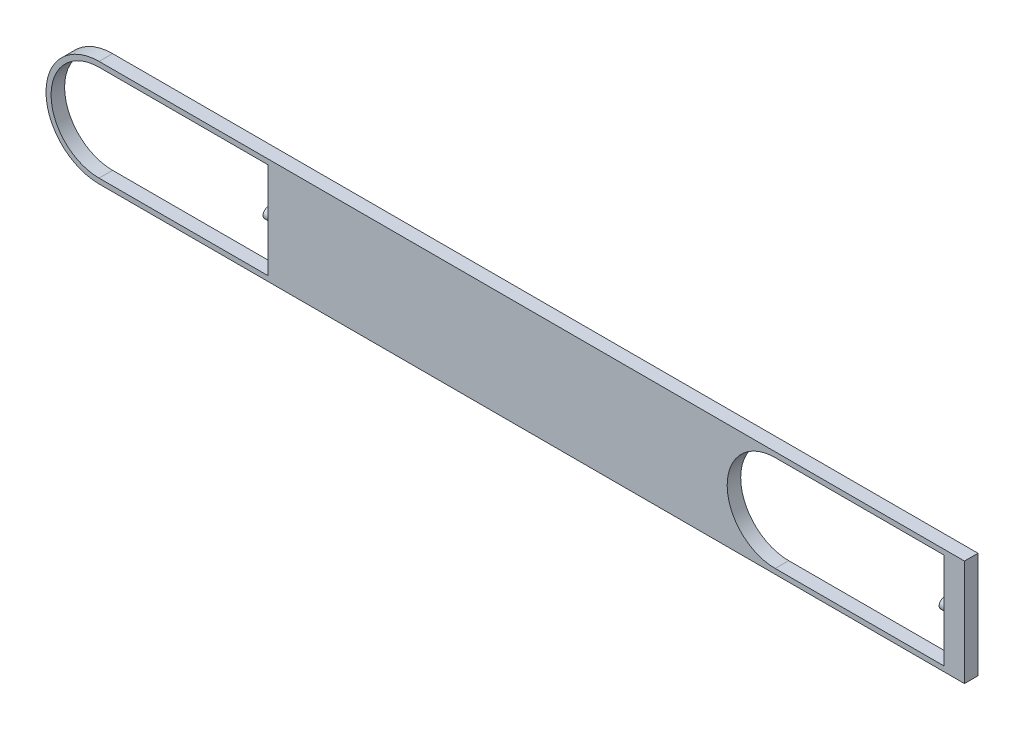
SolidWorks part; units mm, degrees
other "first"
other "second"
ref_plane "Front Plane" through (0, 0, 0) normal (0, 0, 1) x (1, 0, 0)
ref_plane "Top Plane" through (0, 0, 0) normal (0, 1, 0) x (1, 0, 0)
ref_plane "Right Plane" through (0, 0, 0) normal (1, 0, 0) x (0, 0, -1)
sketch "Sketch1" plane through (0, 0, 0) normal (0, 0, 1) x (1, 0, 0)
  circle A0 centre (0, 0) radius 19.939
  dimension "D1" = 39.878
extrude "circle extrude" add sketch "Sketch1" along normal blind 5.08
sketch "Sketch3" plane through (0, 0, 0) normal (1, 0, 0) x (0, 0, -1)
  line L0 (0, 55) -> (0, -55) construction
  line L1 (-5.08, 19.939) -> (0, 19.939)
  line L2 (-5.08, 19.939) -> (-5.08, -19.939)
  line L3 (-5.08, -19.939) -> (0, -19.939)
  line L4 (0, 19.939) -> (0, -19.939)
  line L5 (-5.08, -19.939) -> (0, -19.939) construction
extrude "rectangle extrude" add sketch "Sketch3" along normal blind 127
sketch "Sketch2" plane through (0, 0, 5.08) normal (0, 0, 1) x (1, 0, 0)
  circle A0 centre (0, 0) radius 18.034
  dimension "D1" = 36.068
extrude "circle cut" cut sketch "Sketch2" against normal through all
sketch "Sketch6" plane through (0, 0, 5.08) normal (0, 0, 1) x (1, 0, 0)
  line L1 (125.095, -18.034) -> (125.095, 18.034)
  line L3 (0, -18.034) -> (0, 18.034)
  line L4 (0, -18.034) -> (125.095, -18.034)
  line L5 (127, -19.939) -> (0, -19.939) construction
  line L6 (0, 18.034) -> (125.095, 18.034)
  line L8 (127, 19.939) -> (127, -19.939) construction
  arc A0 (0, 19.939) -> (0, -19.939) centre (0, 0) ccw construction
  circle A1 centre (0, 0) radius 18.034 construction
  point P5 (125.095, 0)
  point P12 (0, 0)
  point P17 (-19.939, 0)
  dimension "D1" = 1.905
  dimension "D2" = 1.905
  dimension "D3" = 19.939
extrude "rectangle cut" cut sketch "Sketch6" against normal through all
sketch "Sketch7" plane through (0, 0, 5.08) normal (0, 0, 1) x (1, 0, 0)
  line L1 (63.5, 18.034) -> (125.095, 18.034)
  line L2 (125.095, -18.034) -> (125.095, 18.034) construction
  line L3 (125.095, 18.034) -> (125.095, -18.034)
  line L4 (125.095, -18.034) -> (63.5, -18.034)
  line L5 (63.5, 18.034) -> (63.5, -18.034)
  line L6 (125.095, 18.034) -> (0, 18.034) construction
  dimension "D2" = 63.5
extrude "end shape" add sketch "Sketch7" against normal blind 5.08
sketch "Sketch8" plane through (63.5, 0, 0) normal (-1, 0, 0) x (0, 0, 1)
  circle A0 centre (2.54, 0) radius 1.905
  dimension "D1" = 3.81
  dimension "D2" = 2.54
extrude "for spring extrude" add sketch "Sketch8" along normal blind 2.54
pattern_linear "mirrored pattern" count 2 spacing 254 along (1, 0, 0) of bodies 109
sketch "Sketch10" plane through (127, 0, 0) normal (1, 0, 0) x (0, 0, -1)
  line L1 (-5.08, 19.939) -> (0, 19.939)
  line L2 (-5.08, 19.939) -> (-5.08, -19.939)
  line L3 (-5.08, -19.939) -> (0, -19.939)
  line L4 (0, 19.939) -> (0, -19.939)
extrude "middle connector" add sketch "Sketch10" along normal up to next
sketch "Sketch11" plane through (381, 0, 0) normal (1, 0, 0) x (0, 0, -1)
  line L1 (-5.08, 19.939) -> (0, 19.939)
  line L2 (-5.08, 19.939) -> (-5.08, -19.939)
  line L3 (-5.08, -19.939) -> (0, -19.939)
  line L4 (0, 19.939) -> (0, -19.939)
extrude "end cut" cut sketch "Sketch11" against normal blind 55.88
